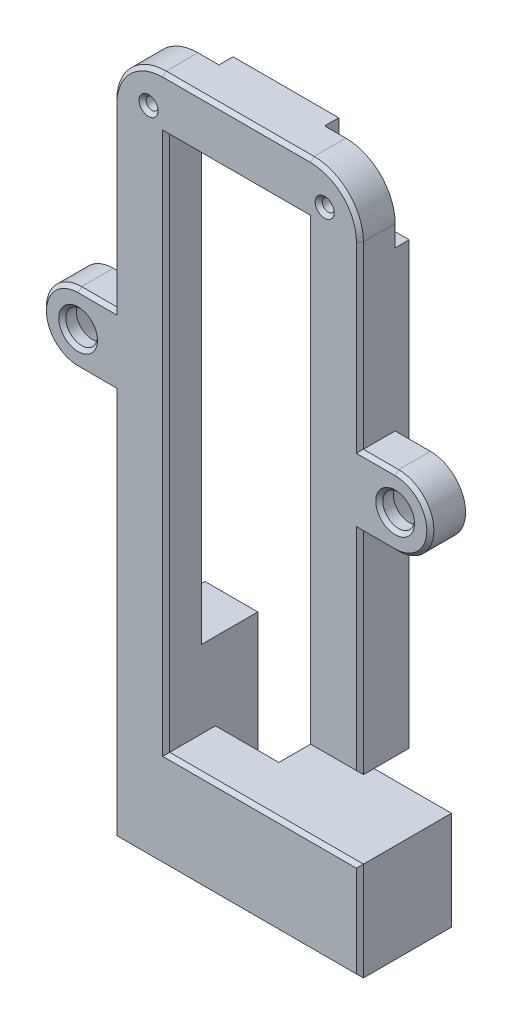
SolidWorks part; units mm, degrees
ref_plane "Front Plane" through (0, 0, 0) normal (0, 0, 1) x (1, 0, 0)
ref_plane "Top Plane" through (0, 0, 0) normal (0, 1, 0) x (1, 0, 0)
ref_plane "Right Plane" through (0, 0, 0) normal (1, 0, 0) x (0, 0, -1)
sketch "Sketch1" plane through (0, 0, 0) normal (0, 0, 1) x (1, 0, 0)
  line L0 (-10, -35) -> (-10, 30)
  line L1 (-15, -35) -> (15, -35) construction
  line L2 (-15, -35) -> (-15, 35) construction
  line L3 (-15, 35) -> (15, 35) construction
  line L4 (15, -35) -> (15, 35) construction
  line L5 (-10, 30) -> (10, 30)
  line L6 (10, 30) -> (10, -35)
  line L7 (-10, -35) -> (-17.5, -35)
  line L8 (-17.5, -35) -> (-17.5, 37.5)
  line L9 (-17.5, 37.5) -> (17.5, 37.5)
  line L10 (17.5, 37.5) -> (17.5, -35)
  line L11 (17.5, -35) -> (10, -35)
  circle A0 centre (-12.5, 32.5) radius 0.85
  circle A1 centre (12.5, 32.5) radius 0.85
  point P4 (0, 35)
  point P5 (-15, 0)
  dimension "D6" = 1.7
  dimension "D1" = 30
  dimension "D2" = 70
  dimension "D3" = 5
  dimension "D4" = 5
  dimension "D5" = 5
  dimension "D7" = 2.5
  dimension "D8" = 2.5
  dimension "D9" = 2.5
  dimension "D10" = 2.5
  dimension "D11" = 7.5
  dimension "D12" = 7.5
  dimension "D13" = 7.5
extrude "Boss-Extrude1" add sketch "Sketch1" along normal blind 5
sketch "Sketch2" plane through (0, 0, 0) normal (0, 0, 1) x (1, 0, 0)
  line L0 (17.5, -35) -> (10, -35) construction
  line L1 (17.5, 37.5) -> (30, 37.5)
  line L2 (17.5, 37.5) -> (17.5, -35)
  line L3 (17.5, -35) -> (15.1, -35)
  line L4 (15.1, 35.1) -> (15.1, -35)
  line L5 (-17.5, 37.5) -> (-30, 37.5)
  line L6 (-17.5, 37.5) -> (-17.5, -35)
  line L7 (-17.5, -35) -> (-15.1, -35)
  line L8 (-15.1, 35.1) -> (-15.1, -35)
  line L9 (30, 37.5) -> (-30, 37.5)
  line L11 (15.1, 35.1) -> (-15.1, 35.1)
  line L12 (15, -35) -> (15, 35) construction
  line L13 (-17.5, -35) -> (-10, -35) construction
  line L15 (-15, -35) -> (-15, 35) construction
  line L16 (-15, 35) -> (15, 35) construction
  dimension "D1" = 0.1
  dimension "D2" = 0.1
  dimension "D3" = 0.1
extrude "Boss-Extrude2" add sketch "Sketch2" against normal blind 2 contours L11 L4 L3 L2 L9 L6 L7 L8 region at (16.6949, 1.25, 0)
sketch "Sketch3" plane through (0, 0, 0) normal (0, 0, 1) x (1, 0, 0)
  line L0 (17.5, 37.5) -> (17.5, -35) construction
  line L1 (22.5, 5) -> (17.5, 5)
  line L3 (22.5, -5) -> (17.5, -5)
  line L4 (17.5, 5) -> (17.5, -5)
  line L5 (-17.5, -35) -> (-17.5, 37.5) construction
  line L6 (-22.5, 5) -> (-17.5, 5)
  line L8 (-22.5, -5) -> (-17.5, -5)
  line L9 (-17.5, 5) -> (-17.5, -5)
  arc A0 (22.5, -5) -> (22.5, 5) centre (22.5, 0) ccw
  arc A1 (-22.5, 5) -> (-22.5, -5) centre (-22.5, 0) ccw
  circle A2 centre (22.5, 0) radius 2.25
  circle A3 centre (-22.5, 0) radius 2.25
  dimension "D1" = 10
  dimension "D2" = 10
  dimension "D3" = 4.5
  dimension "D4" = 4.5
extrude "Boss-Extrude3" add sketch "Sketch3" along normal up to surface (5 mm away) up to face at (0, -0.625, 5)
sketch "Sketch4" plane through (0, 0, 0) normal (0, 0, -1) x (-1, 0, 0)
  circle A0 centre (-22.5, 0) radius 3.5
  circle A1 centre (22.5, 0) radius 3.5
  dimension "D1" = 7
  dimension "D2" = 7
extrude "Cut-Extrude1" cut sketch "Sketch4" against normal blind 3
sketch "Sketch5" plane through (0, 0, 0) normal (0, 0, -1) x (-1, 0, 0)
  line L1 (-7.5, 37.5) -> (-17.5, 37.5)
  line L2 (-7.5, 37.5) -> (-7.5, 27.5)
  line L3 (-7.5, 27.5) -> (-17.5, 27.5)
  line L4 (-17.5, 37.5) -> (-17.5, 27.5)
  line L5 (-7.5, 37.5) -> (-17.5, 27.5) construction
  line L6 (-7.5, 27.5) -> (-17.5, 37.5) construction
  line L7 (7.5, 37.5) -> (17.5, 37.5)
  line L8 (7.5, 37.5) -> (7.5, 27.5)
  line L9 (7.5, 27.5) -> (17.5, 27.5)
  line L10 (17.5, 37.5) -> (17.5, 27.5)
  line L11 (7.5, 37.5) -> (17.5, 27.5) construction
  line L12 (7.5, 27.5) -> (17.5, 37.5) construction
  point P0 (-12.5, 32.5)
  point P5 (12.5, 32.5)
  point P12 (0, 0)
  point P13 (0, 0)
  point P17 (20.8445, 36.306)
extrude "Cut-Extrude2" cut sketch "Sketch5" along normal through all
fillet "Fillet1" radius 7 2 edges at (-17.5, 37.5, 2.5) (17.5, 37.5, 2.5)
sketch "Sketch6" plane through (0, 0, 0) normal (0, 0, 1) x (1, 0, 0)
  line L1 (-17.5, -35) -> (-10, -35)
  line L2 (-17.5, -35) -> (-17.5, -60)
  line L3 (-17.5, -60) -> (-10, -60)
  line L4 (-10, -35) -> (-10, -60)
  line L5 (-10, -35) -> (-10, 30) construction
  dimension "D1" = 25
extrude "Boss-Extrude4" add sketch "Sketch6" along normal up to surface (5 mm away) and the other way blind 8 up to face at (0, 3.2722, 5)
sketch "Sketch7" plane through (-10, 0, 0) normal (1, 0, 0) x (0, 0, -1)
  line L0 (8, -35) -> (0, -35) construction
  line L1 (-5, -60) -> (2, -60)
  line L2 (-5, -60) -> (-5, -46)
  line L3 (-5, -46) -> (2, -46)
  line L4 (2, -60) -> (2, -46)
  line L5 (0, -35) -> (0, 30) construction
  dimension "D1" = 11
  dimension "D2" = 2
extrude "Boss-Extrude5" add sketch "Sketch7" along normal up to surface (27.5 mm away) up to face at (17.5, 4.6, 1.6)
sketch "Sketch8" plane through (0, 0, -2) normal (0, 0, -1) x (-1, 0, 0)
  line L1 (-17.5, -46) -> (1, -46)
  line L2 (-17.5, -46) -> (-17.5, -60)
  line L3 (-17.5, -60) -> (1, -60)
  line L4 (1, -46) -> (1, -60)
  line L5 (-17.5, -60) -> (10, -60) construction
  line L6 (10, -60) -> (10, -46) construction
  point P4 (0.8797, -60)
  point P7 (0, 0)
  dimension "D1" = 9
extrude "Boss-Extrude6" add sketch "Sketch8" along normal up to surface (6 mm away) up to face at (-13.75, -47.5, -8)
chamfer "Chamfer3" distance 0.5 angle 45 26 edges at (-24.75, 0, 5) (20.25, 0, 5) (13.35, 32.5, 5) (-11.65, 32.5, 5) (-17.5, -32.5, 5) (-20, -5, 5) (-27.5, 0, 5) (-20, 5, 5) (-17.5, 17.75, 5) (0, 37.5, 5) (17.5, 17.75, 5) (20, 5, 5) (27.5, 0, 5) (20, -5, 5) (17.5, -20, 5) (13.75, -35, 5) (10, -2.5, 5) (0, 30, 5) (-10, -8, 5) (-11.65, 32.5, 0) (13.35, 32.5, 0) (15.4497, 35.4497, 5) (-15.4497, 35.4497, 5) (0, -60, 5) (3.75, -46, 5) (17.5, -53, 5)
chamfer "Chamfer1" distance 2.5 distance2 1.25 2 edges at (-26, 0, 3) (19, 0, 3) first distance on face at (-26, 0, 3) first distance on face at (19, 0, 3)
